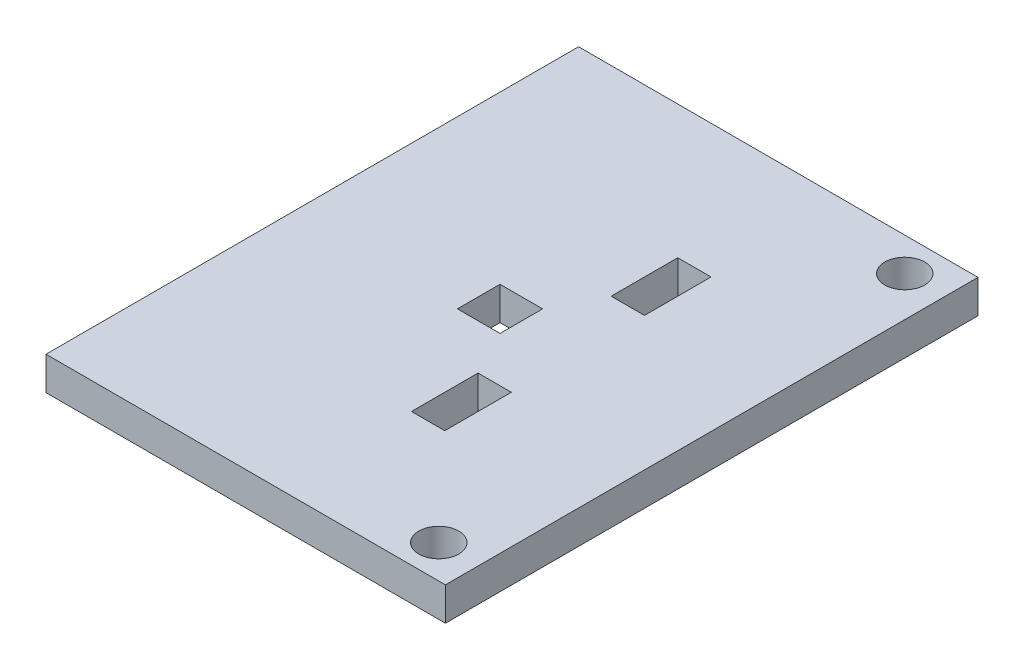
SolidWorks part; units mm, degrees
ref_plane "Front Plane" through (0, 0, 0) normal (0, 0, 1) x (1, 0, 0)
ref_plane "Top Plane" through (0, 0, 0) normal (0, 1, 0) x (1, 0, 0)
ref_plane "Right Plane" through (0, 0, 0) normal (1, 0, 0) x (0, 0, -1)
sketch "Sketch1" plane through (0, 0, 0) normal (0, 1, 0) x (1, 0, 0)
  line L1 (0, 0) -> (76.2, 0)
  line L2 (0, 0) -> (0, 101.6)
  line L3 (0, 101.6) -> (76.2, 101.6)
  line L4 (76.2, 0) -> (76.2, 101.6)
  dimension "D1" = 76.2
  dimension "D2" = 101.6
extrude "Boss-Extrude1" add sketch "Sketch1" along normal blind 6.35
sketch "Sketch2" plane through (0, 6.35, 0) normal (0, 1, 0) x (1, 0, 0)
  line L0 (68.58, 0) -> (68.58, 101.6) construction
  line L1 (0, 0) -> (76.2, 0) construction
  line L2 (76.2, 101.6) -> (0, 101.6) construction
  line L3 (0, 6.35) -> (76.2, 6.35) construction
  line L4 (0, 101.6) -> (0, 0) construction
  line L5 (76.2, 0) -> (76.2, 101.6) construction
  line L6 (0, 95.25) -> (76.2, 95.25) construction
  line L7 (38.1, 95.25) -> (38.1, 6.35) construction
  line L8 (47.498, 69.85) -> (47.498, 31.75) construction
  line L9 (44.323, 76.2) -> (50.673, 76.2)
  line L10 (44.323, 76.2) -> (44.323, 63.5)
  line L11 (44.323, 63.5) -> (50.673, 63.5)
  line L12 (50.673, 76.2) -> (50.673, 63.5)
  line L13 (44.323, 76.2) -> (50.673, 63.5) construction
  line L14 (44.323, 63.5) -> (50.673, 76.2) construction
  line L15 (44.323, 38.1) -> (50.673, 38.1)
  line L16 (44.323, 38.1) -> (44.323, 25.4)
  line L17 (44.323, 25.4) -> (50.673, 25.4)
  line L18 (50.673, 38.1) -> (50.673, 25.4)
  line L19 (44.323, 38.1) -> (50.673, 25.4) construction
  line L20 (44.323, 25.4) -> (50.673, 38.1) construction
  line L21 (0, 50.8) -> (76.2, 50.8) construction
  line L23 (31.75, 54.864) -> (39.878, 54.864)
  line L24 (31.75, 54.864) -> (31.75, 46.736)
  line L25 (31.75, 46.736) -> (39.878, 46.736)
  line L26 (39.878, 54.864) -> (39.878, 46.736)
  line L27 (31.75, 54.864) -> (39.878, 46.736) construction
  line L28 (31.75, 46.736) -> (39.878, 54.864) construction
  circle A0 centre (68.58, 95.25) radius 3.81
  circle A1 centre (68.58, 6.35) radius 3.81
  point P18 (47.498, 69.85)
  point P25 (47.498, 31.75)
  point P32 (35.814, 50.8)
  dimension "D4" = 7.62
  dimension "D5" = 25.4
  dimension "D1" = 6.35
  dimension "D2" = 6.35
  dimension "D3" = 7.62
  dimension "D6" = 6.35
  dimension "D7" = 6.35
  dimension "D8" = 12.7
  dimension "D9" = 12.7
  dimension "D10" = 12.7
  dimension "D11" = 8.128
  dimension "D12" = 10.795
  dimension "D13" = 31.75
  dimension "D14" = 8.128
extrude "Cut-Extrude1" cut sketch "Sketch2" against normal through all
